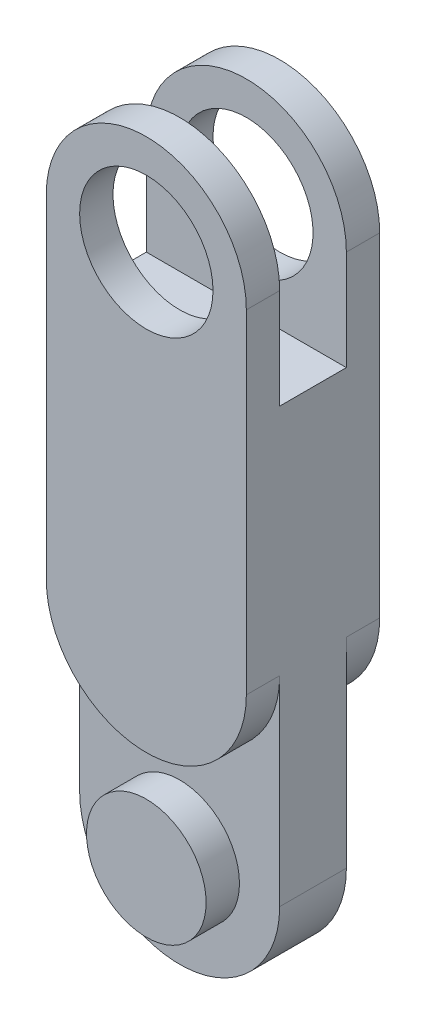
SolidWorks part; units mm, degrees
ref_plane "Alzado" through (0, 0, 0) normal (0, 0, 1) x (1, 0, 0)
ref_plane "Planta" through (0, 0, 0) normal (0, 1, 0) x (1, 0, 0)
ref_plane "Vista lateral" through (0, 0, 0) normal (1, 0, 0) x (0, 0, -1)
sketch "Croquis1" plane through (0, 0, 0) normal (0, 0, 1) x (1, 0, 0)
  line L0 (0, 0) -> (0, 80) construction
  line L7 (-15, 0) -> (-15, 80)
  line L8 (15, 80) -> (15, 0)
  arc A2 (15, 80) -> (-15, 80) centre (0, 80) ccw
  arc A3 (-15, 0) -> (15, 0) centre (0, 0) ccw
  circle A4 centre (0, 80) radius 10
  dimension "D2" = 20
  dimension "D3" = 30
  dimension "D1" = 30
  dimension "D5" = 80
extrude "Saliente-Extruir1" add sketch "Croquis1" along normal mid plane 20
sketch "Croquis2" plane through (0, 0, 0) normal (1, 0, 0) x (0, 0, -1)
  line L0 (-10, 80) -> (10, 80) construction
  line L1 (5, 65) -> (-5, 65)
  line L2 (5, 65) -> (5, 95)
  line L3 (5, 95) -> (-5, 95)
  line L4 (-5, 65) -> (-5, 95)
  line L5 (5, 65) -> (-5, 95) construction
  line L6 (5, 95) -> (-5, 65) construction
  line L7 (10, 95) -> (-10, 95) construction
  line L8 (-10, 95) -> (-10, 80) construction
  line L11 (-3.8212, -15) -> (3.8212, -15)
  line L13 (10, 80) -> (10, 95) construction
  line L15 (-10, -15) -> (10, -15) construction
  point P0 (0, 80)
  dimension "D1" = 5
  dimension "D2" = 5
extrude "Cortar-Extruir2" cut sketch "Croquis2" against normal through all both and the other way through all contours L2 L1 L4 L3
sketch "Croquis4" plane through (0, 0, 0) normal (0, 0, 1) x (1, 0, 0)
  line L0 (-15, 30) -> (-15, 0)
  line L1 (15, 30) -> (15, 0)
  circle A0 centre (0, 0) radius 8.9685
  arc A1 (-15, 0) -> (15, 0) centre (0, 0) ccw
  arc A2 (-15, 30) -> (15, 30) centre (0, 30) ccw
extrude "Cortar-Extruir4" cut sketch "Croquis4" against normal through all from offset 5 offset against normal yes
extrude "Cortar-Extruir6" cut sketch "Croquis4<2>" along normal through all from offset 5
sketch "Croquis4<2>" plane through (0, 0, 0) normal (0, 0, 1) x (1, 0, 0) same geometry as "Croquis4"
